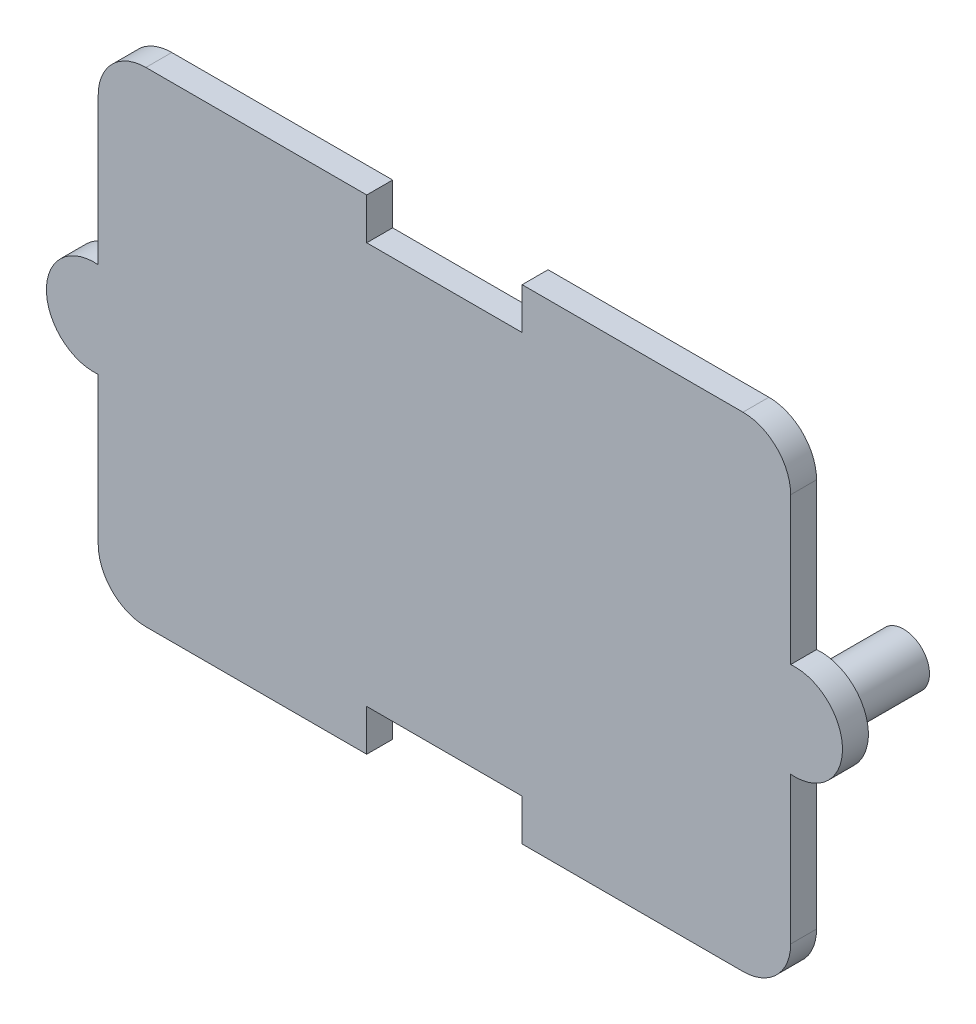
SolidWorks part; units mm, degrees
material "PET"
ref_plane "Front Plane" through (0, 0, 0) normal (0, 0, 1) x (1, 0, 0)
ref_plane "Top Plane" through (0, 0, 0) normal (0, 1, 0) x (1, 0, 0)
ref_plane "Right Plane" through (0, 0, 0) normal (1, 0, 0) x (0, 0, -1)
sketch "Sketch1" plane through (0, 0, 0) normal (0, 0, 1) x (1, 0, 0)
  line L6 (21.4725, 3.175) -> (21.4725, 11.9225) construction
  line L7 (21.4725, -11.9225) -> (21.4725, -3.175) construction
  line L8 (-18.2975, -15.0975) -> (18.2975, -15.0975) construction
  line L9 (-21.4725, -3.175) -> (-21.4725, -11.9225) construction
  line L10 (-21.4725, 3.175) -> (-21.4725, 11.9225) construction
  line L11 (18.2975, 15.0975) -> (-18.2975, 15.0975) construction
  line L12 (-21.4725, 0) -> (21.4725, 0) construction
  line L13 (0, 15.0975) -> (0, -15.0975) construction
  arc A6 (21.4725, 11.9225) -> (18.2975, 15.0975) centre (18.2975, 11.9225) ccw construction
  arc A7 (21.4725, -3.175) -> (21.4725, 3.175) centre (21.4725, 0) ccw construction
  arc A8 (18.2975, -15.0975) -> (21.4725, -11.9225) centre (18.2975, -11.9225) ccw construction
  arc A9 (-21.4725, -11.9225) -> (-18.2975, -15.0975) centre (-18.2975, -11.9225) ccw construction
  arc A10 (-21.4725, 3.175) -> (-21.4725, -3.175) centre (-21.4725, 0) ccw construction
  arc A11 (-18.2975, 15.0975) -> (-21.4725, 11.9225) centre (-18.2975, 11.9225) ccw construction
  dimension "D1" = 3.175
  dimension "D2" = 21.4725
  dimension "D3" = 15.0975
sketch "Sketch2" plane through (0, 0, 0) normal (0, 0, 1) x (1, 0, 0)
  line L53 (21.2185, 2.9099) -> (21.2185, 11.9225)
  line L54 (21.2185, -11.9225) -> (21.2185, -2.9099)
  line L55 (-18.2975, -14.8435) -> (18.2975, -14.8435)
  line L56 (-21.2185, -2.9099) -> (-21.2185, -11.9225)
  line L57 (-21.2185, 11.9225) -> (-21.2185, 2.9099)
  line L58 (18.2975, 14.8435) -> (-18.2975, 14.8435)
  line L59 (21.2185, 2.9099) -> (21.2185, 11.9225)
  line L60 (21.2185, -11.9225) -> (21.2185, -2.9099)
  line L61 (-18.2975, -14.8435) -> (18.2975, -14.8435)
  line L62 (-21.2185, -2.9099) -> (-21.2185, -11.9225)
  line L63 (-21.2185, 11.9225) -> (-21.2185, 2.9099)
  line L64 (18.2975, 14.8435) -> (-18.2975, 14.8435)
  arc A42 (21.2185, 11.9225) -> (18.2975, 14.8435) centre (18.2975, 11.9225) ccw
  arc A43 (21.2185, -2.9099) -> (21.2185, 2.9099) centre (21.4725, 0) ccw
  arc A44 (18.2975, -14.8435) -> (21.2185, -11.9225) centre (18.2975, -11.9225) ccw
  arc A45 (-21.2185, -11.9225) -> (-18.2975, -14.8435) centre (-18.2975, -11.9225) ccw
  arc A46 (-21.2185, 2.9099) -> (-21.2185, -2.9099) centre (-21.4725, 0) ccw
  arc A47 (-18.2975, 14.8435) -> (-21.2185, 11.9225) centre (-18.2975, 11.9225) ccw
  arc A48 (21.2185, 11.9225) -> (18.2975, 14.8435) centre (18.2975, 11.9225) ccw
  arc A49 (21.2185, -2.9099) -> (21.2185, 2.9099) centre (21.4725, 0) ccw
  arc A50 (18.2975, -14.8435) -> (21.2185, -11.9225) centre (18.2975, -11.9225) ccw
  arc A51 (-21.2185, -11.9225) -> (-18.2975, -14.8435) centre (-18.2975, -11.9225) ccw
  arc A52 (-21.2185, 2.9099) -> (-21.2185, -2.9099) centre (-21.4725, 0) ccw
  arc A53 (-18.2975, 14.8435) -> (-21.2185, 11.9225) centre (-18.2975, 11.9225) ccw
  dimension "D1" = 0.254
extrude "Boss-Extrude1" add sketch "Sketch2" along normal blind 1.5875
sketch "Sketch3" plane through (0, 0, 1.5875) normal (0, 0, 1) x (1, 0, 0)
  line L0 (-18.2975, -14.8435) -> (18.2975, -14.8435) construction
  line L1 (-4.7625, -14.8435) -> (4.7625, -14.8435)
  line L2 (-4.7625, -14.8435) -> (-4.7625, -12.3035)
  line L3 (-4.7625, -12.3035) -> (4.7625, -12.3035)
  line L4 (4.7625, -14.8435) -> (4.7625, -12.3035)
  line L5 (0, 0) -> (0, -12.3035) construction
  line L6 (18.2975, 14.8435) -> (-18.2975, 14.8435) construction
  line L7 (4.7625, 14.8435) -> (-4.7625, 14.8435)
  line L8 (4.7625, 14.8435) -> (4.7625, 12.3035)
  line L9 (4.7625, 12.3035) -> (-4.7625, 12.3035)
  line L10 (-4.7625, 14.8435) -> (-4.7625, 12.3035)
  dimension "D1" = 2.54
  dimension "D2" = 9.525
extrude "Cut-Extrude1" cut sketch "Sketch3" against normal through all
sketch "Sketch4" plane through (0, 0, 0) normal (0, 0, -1) x (-1, 0, 0)
  circle A0 centre (-21.4725, 0) radius 1.5875
  circle A1 centre (21.4725, 0) radius 1.5875
  dimension "D1" = 3.175
  dimension "D2" = 3.175
extrude "Boss-Extrude2" add sketch "Sketch4" along normal blind 5.08
